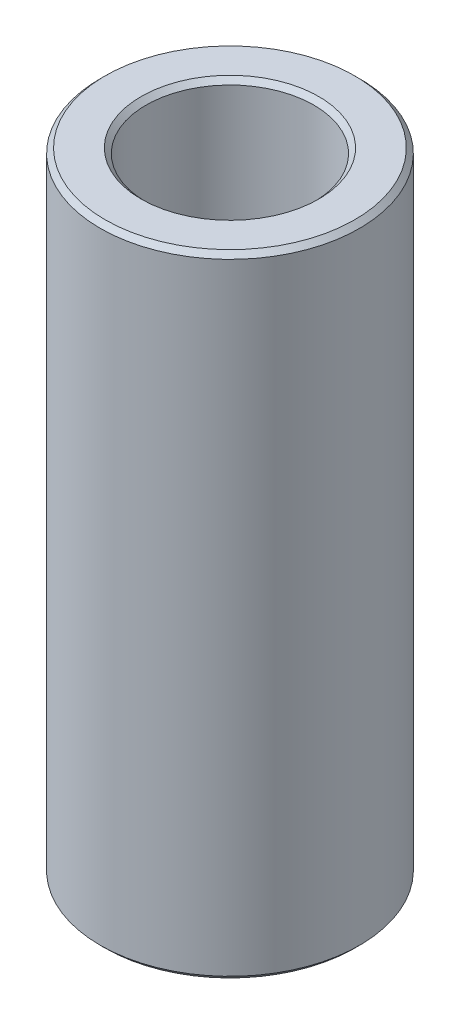
SolidWorks part; units mm, degrees
ref_plane "Front Plane" through (0, 0, 0) normal (0, 0, 1) x (1, 0, 0)
ref_plane "Top Plane" through (0, 0, 0) normal (0, 1, 0) x (1, 0, 0)
ref_plane "Right Plane" through (0, 0, 0) normal (1, 0, 0) x (0, 0, -1)
sketch "Sketch1" plane through (0, 0, 0) normal (0, 1, 0) x (1, 0, 0)
  circle A0 centre (0, 0) radius 57.5
  dimension "SLEEVE_OD" = 115
extrude "Boss-Extrude1" add sketch "Sketch1" along normal blind 279.667
sketch "Sketch2" plane through (0, 0, 0) normal (0, 1, 0) x (1, 0, 0)
  circle A0 centre (0, 0) radius 37.2036
  dimension "BORE_D" = 74.4073
extrude "Cut-Extrude1" cut sketch "Sketch2" along normal through all
chamfer "Chamfer1" distance 2.191 angle 45 4 edges at (0, 279.667, 37.2036) (0, 0, 37.2036) (0, 0, 57.5) (0, 279.667, 57.5)
